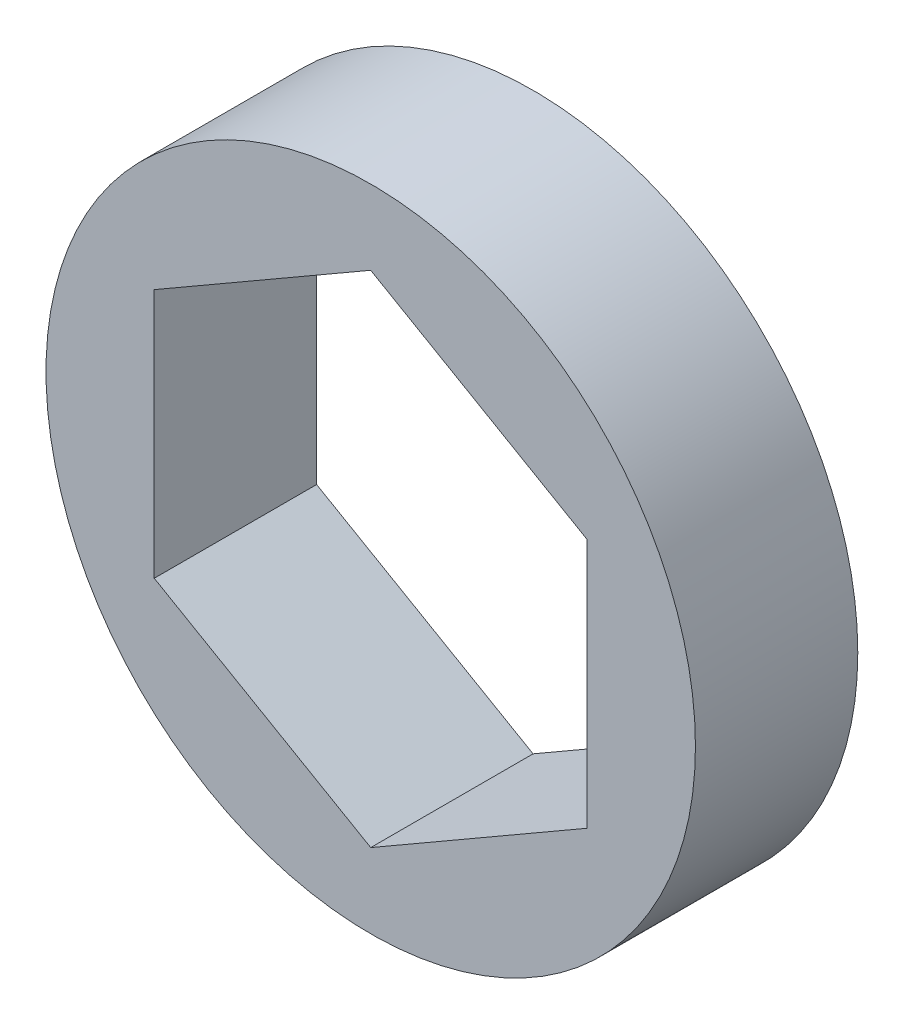
SolidWorks part; units mm, degrees
material "Nylon 101"
ref_plane "Front Plane" through (0, 0, 0) normal (0, 0, 1) x (1, 0, 0)
ref_plane "Top Plane" through (0, 0, 0) normal (0, 1, 0) x (1, 0, 0)
ref_plane "Right Plane" through (0, 0, 0) normal (1, 0, 0) x (0, 0, -1)
sketch "Sketch2" plane through (0, 0, 0) normal (0, 0, 1) x (1, 0, 0)
  line L1 (0, 7.3323) -> (-6.35, 3.6662)
  line L2 (-6.35, 3.6662) -> (-6.35, -3.6662)
  line L3 (-6.35, -3.6662) -> (0, -7.3323)
  line L4 (0, -7.3323) -> (6.35, -3.6662)
  line L5 (6.35, -3.6662) -> (6.35, 3.6662)
  line L6 (6.35, 3.6662) -> (0, 7.3323)
  circle A0 centre (0, 0) radius 6.35 construction
  circle A1 centre (0, 0) radius 9.525
  dimension "D1" = 19.05
  dimension ".5" = 12.7
extrude "Boss-Extrude1" add sketch "Sketch2" along normal blind 4.7625
